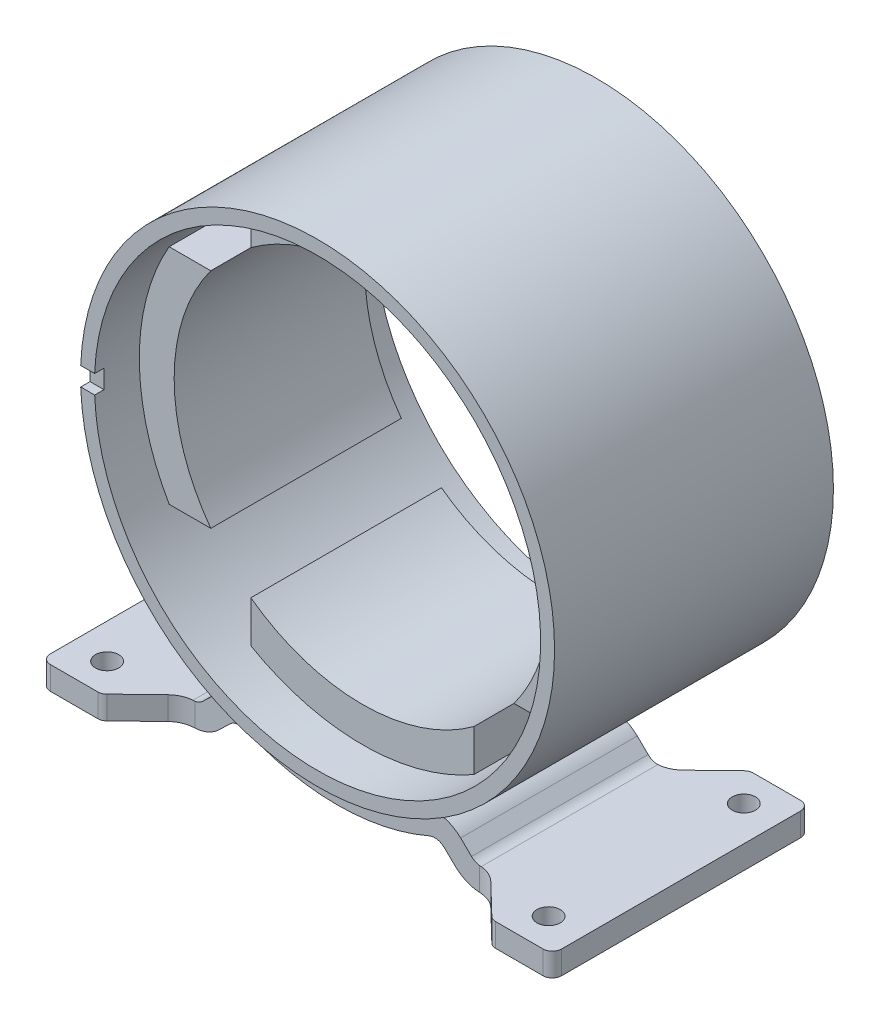
SolidWorks part; units mm, degrees
material "Acier non allié"
ref_plane "Plan de face" through (0, 0, 0) normal (0, 0, 1) x (1, 0, 0)
ref_plane "Plan de dessus" through (0, 0, 0) normal (0, 1, 0) x (1, 0, 0)
ref_plane "Plan de droite" through (0, 0, 0) normal (1, 0, 0) x (0, 0, -1)
sketch "Esquisse1" plane through (0, 0, 0) normal (0, 0, 1) x (1, 0, 0)
  circle A0 centre (0, 0) radius 48
  circle A1 centre (0, 0) radius 51
  dimension "D1" = 102
  dimension "D2" = 96
extrude "Boss.-Extru.1" add sketch "Esquisse1" along normal blind 60
sketch "Esquisse3" plane through (0, 0, 0) normal (0, 0, 1) x (1, 0, 0)
  line L0 (-41.5692, 24) -> (-32.6228, 24)
  line L1 (-41.5692, -24) -> (-32.6228, -24)
  line L2 (-24, 0) -> (24, 0) construction
  line L3 (-24, 41.5692) -> (-24, 32.6228)
  line L4 (24, 41.5692) -> (24, 32.6228)
  line L5 (0, 52) -> (0, -52) construction
  line L9 (32.6228, 24) -> (41.5692, 24)
  line L10 (-32.6228, 24) -> (-32.6228, -24) construction
  line L11 (24, -32.6228) -> (24, -41.5692)
  line L12 (32.6228, -24) -> (41.5692, -24)
  line L13 (-24, -32.6228) -> (-24, -41.5692)
  line L14 (-24, 32.6228) -> (24, 32.6228) construction
  arc A0 (-32.6228, 24) -> (-32.6228, -24) centre (0, 0) ccw
  arc A1 (-41.5692, 24) -> (-41.5692, -24) centre (0, 0) ccw
  arc A2 (-24, -41.5692) -> (24, -41.5692) centre (0, 0) ccw
  arc A3 (41.5692, -24) -> (41.5692, 24) centre (0, 0) ccw
  arc A4 (32.6228, -24) -> (32.6228, 24) centre (0, 0) ccw
  arc A5 (24, 32.6228) -> (-24, 32.6228) centre (0, 0) ccw
  arc A6 (-24, -32.6228) -> (24, -32.6228) centre (0, 0) ccw
  arc A7 (24, 41.5692) -> (-24, 41.5692) centre (0, 0) ccw
  circle A8 centre (0, 0) radius 48 construction
  dimension "D7" = 81
  dimension "D2" = 48
extrude "Boss.-Extru.2" add sketch "Esquisse3" along normal blind 41 from offset 9.35
sketch "Esquisse4" plane through (0, 0, 0) normal (0, 0, 1) x (1, 0, 0)
  line L0 (28.9116, -51.6535) -> (26.5693, -49.3822)
  line L1 (55, -52.4998) -> (31, -52.4998)
  line L2 (-55, -57.5) -> (-31, -57.5)
  line L3 (-23.0884, -52.9719) -> (-25.4307, -55.2431)
  line L4 (0, -6.9086) -> (0, -68.6957) construction
  line L5 (-55, -57.5) -> (-55, -52.4998)
  line L6 (-55, -52.4998) -> (-31, -52.4998)
  line L7 (-28.9116, -51.6535) -> (-26.5693, -49.3822)
  line L8 (55, -57.5) -> (55, -52.4998)
  line L9 (23.0884, -52.9719) -> (25.4307, -55.2431)
  line L10 (55, -57.5) -> (31, -57.5)
  arc A0 (-19.8021, -52.3751) -> (19.8021, -52.3751) centre (0, -6.9086) ccw
  arc A1 (-17.8055, -47.7908) -> (17.8055, -47.7908) centre (0, -6.9086) ccw
  circle A2 centre (0, 0) radius 51 construction
  arc A3 (-28.9116, -51.6535) -> (-31, -52.4998) centre (-31, -49.4998) cw
  arc A4 (-25.4307, -55.2431) -> (-31, -57.5) centre (-31, -49.4998) cw
  arc A5 (-23.0884, -52.9719) -> (-19.8021, -52.3751) centre (-21, -55.1255) cw
  arc A6 (-26.5693, -49.3822) -> (-17.8055, -47.7908) centre (-21, -55.1255) cw
  arc A7 (26.5693, -49.3822) -> (17.8055, -47.7908) centre (21, -55.1255) ccw
  arc A8 (23.0884, -52.9719) -> (19.8021, -52.3751) centre (21, -55.1255) ccw
  arc A9 (25.4307, -55.2431) -> (31, -57.5) centre (31, -49.4998) ccw
  arc A10 (28.9116, -51.6535) -> (31, -52.4998) centre (31, -49.4998) ccw
  dimension "D5" = 3
  dimension "D6" = 3
  dimension "D7" = 0.5
  dimension "D8" = 6.5
  dimension "D9" = 42
  dimension "D3" = 5.0002
  dimension "D1" = 57.5
  dimension "D2" = 110
  dimension "D4" = 24
extrude "Boss.-Extru.3" add sketch "Esquisse4" along normal blind 55.4 from offset 9.08 separate body
sketch "Esquisse5" plane through (0, 0, 0) normal (0, 1, 0) x (1, 0, 0)
  line L0 (-55, -36.78) -> (0, -36.78) construction
  line L1 (-55, -64.48) -> (-55, -9.08) construction
  line L2 (0, 0) -> (0, -36.78) construction
  line L3 (-33, -17.78) -> (33, -17.78)
  line L4 (-33, -17.78) -> (-42, -9.08)
  line L5 (33, -17.78) -> (42, -9.08)
  line L8 (-42, -9.08) -> (42, -9.08)
  line L9 (17.8055, -9.08) -> (-17.8055, -9.08) construction
  line L10 (-42, -64.48) -> (42, -64.48)
  line L11 (33, -55.78) -> (42, -64.48)
  line L12 (-33, -55.78) -> (-42, -64.48)
  line L13 (-33, -55.78) -> (33, -55.78)
  dimension "D1" = 13
  dimension "D2" = 38
  dimension "D3" = 22
extrude "Enlèv. mat.-Extru.1" cut sketch "Esquisse5" against normal through all
fillet "Congé1" radius 2 8 edges at (42, -54.9999, 64.48) (55, -54.9999, 64.48) (55, -54.9999, 9.08) (42, -54.9999, 9.08) (-42, -54.9999, 9.08) (-55, -54.9999, 9.08) (-55, -54.9999, 64.48) (-42, -54.9999, 64.48)
fillet "Congé2" radius 6 4 edges at (-33, -54.9999, 55.78) (-33, -54.9999, 17.78) (33, -54.9999, 17.78) (33, -54.9999, 55.78)
hole_wizard "Trou taraudé M61" positions "Esquisse10" profile "Esquisse9" tap size "M6" standard "ISO" end condition up to next
sketch "Esquisse10" plane through (0, -57.5, 0) normal (0, -1, 0) x (-1, 0, 0)
  line L1 (-47.5, -15.78) -> (47.5, -15.78) construction
  line L2 (-47.5, -15.78) -> (-47.5, -57.78) construction
  line L3 (-47.5, -57.78) -> (47.5, -57.78) construction
  line L4 (47.5, -15.78) -> (47.5, -57.78) construction
  line L5 (0, -15.78) -> (0, 0) construction
  line L6 (-55, -36.78) -> (-47.5, -36.78) construction
  line L7 (-55, -62.48) -> (-55, -11.08) construction
  point P0 (47.5, -57.78)
  point P4 (47.5, -15.78)
  point P7 (-47.5, -15.78)
  point P10 (-47.5, -57.78)
  dimension "D1" = 42
  dimension "D2" = 95
sketch "Esquisse9" plane through (-47.5, -57.5, 57.78) normal (1, 0, 0) x (0, 0, -1)
  line L0 (0, 0) -> (0, 50.5899)
  line L1 (0, 50.5899) -> (2.5, 50.5899)
  line L2 (2.5, 50.5899) -> (2.5, 0)
  line L5 (2.5, 0) -> (0, 0)
  line L11 (0, -6.35) -> (0, 107.95) construction
  dimension "Diamètre du trou pour taraudage jusqu'au prochain" = 5
  dimension "Profondeur du trou pour taraudage jusqu'au prochain" = 50.5899
cosmetic thread "Filetage de perçage1" parameters "D2"=6
cosmetic thread "Filetage de perçage2" parameters "D2"=6
cosmetic thread "Filetage de perçage3" parameters "D2"=6
cosmetic thread "Filetage de perçage4" parameters "D2"=6
ref_plane "Plan référence MAP" through (0, 0, 57.78) normal (0, 0, -1) x (-1, 0, 0)
chamfer "Chanfrein1" distance 0.5 angle 45 4 edges at (-47.5, -57.5, 13.28) (-47.5, -57.5, 55.28) (47.5, -57.5, 55.28) (47.5, -57.5, 13.28)
sketch "Esquisse6" plane through (0, 0, 60) normal (0, 0, 1) x (1, 0, 0)
  line L0 (0, 0) -> (-15.943, 0) construction
  line L1 (-51, 2) -> (-47.9583, 2)
  line L3 (-51, -2) -> (-47.9583, -2)
  line L5 (-51, 2) -> (-51, -2)
  line L6 (-47.9583, 2) -> (-47.9583, -2)
  circle A1 centre (0, 0) radius 51 construction
  arc A3 (-41.5692, 24) -> (-41.5692, -24) centre (0, 0) ccw construction
  dimension "D1" = 4
extrude "Enlèv. mat.-Extru.2" cut sketch "Esquisse6" against normal blind 2
sketch "Esquisse7" plane through (0, 0, 0) normal (0, 0, -1) x (-1, 0, 0)
  line L0 (0, 0) -> (-8.325, 0) construction
  line L1 (47.9583, 2) -> (51, 2)
  line L2 (47.9583, 2) -> (47.9583, -2)
  line L3 (47.9583, -2) -> (51, -2)
  line L5 (51, 2) -> (51, -2)
  circle A0 centre (0, 0) radius 48 construction
  circle A2 centre (0, 0) radius 51 construction
  dimension "D1" = 4
extrude "Enlèv. mat.-Extru.3" cut sketch "Esquisse7" against normal blind 2.5
